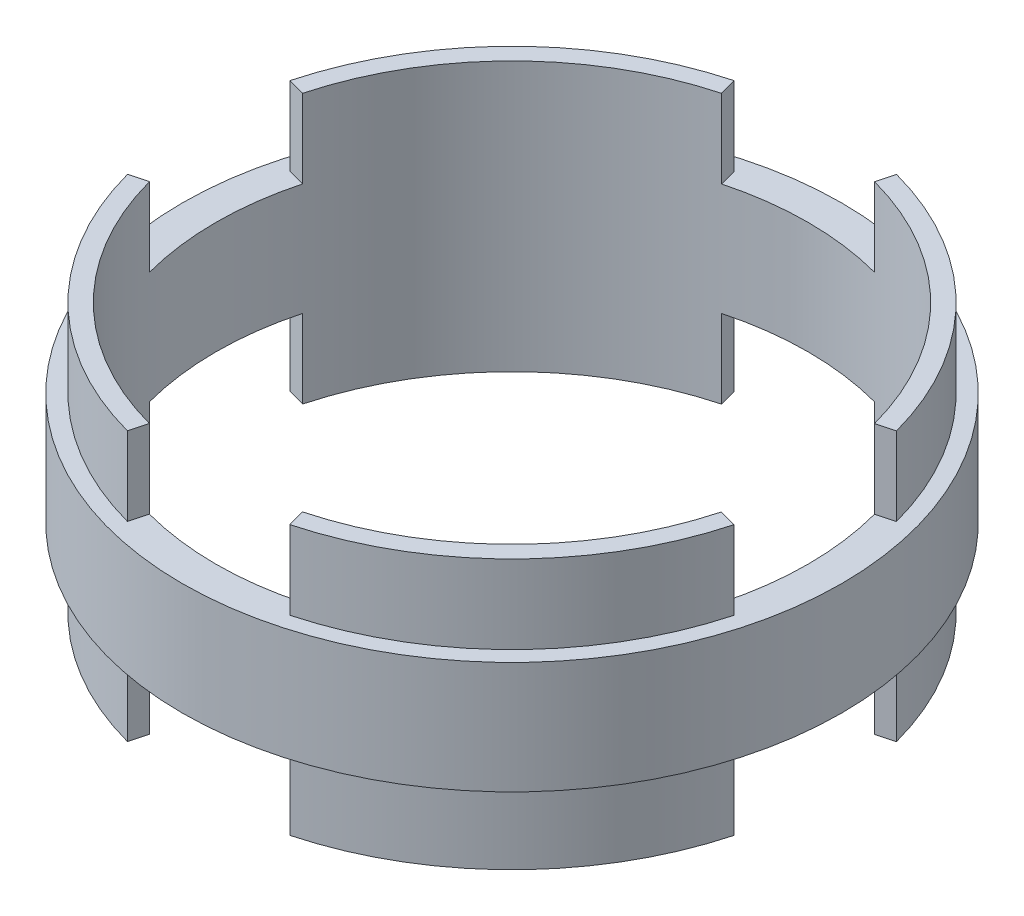
SolidWorks part; units mm, degrees
ref_plane "Front Plane" through (0, 0, 0) normal (0, 0, 1) x (1, 0, 0)
ref_plane "Top Plane" through (0, 0, 0) normal (0, 1, 0) x (1, 0, 0)
ref_plane "Right Plane" through (0, 0, 0) normal (1, 0, 0) x (0, 0, -1)
sketch "Sketch1" plane through (0, 0, 0) normal (0, 1, 0) x (1, 0, 0)
  circle A0 centre (0, 0) radius 93.345
  circle A1 centre (0, 0) radius 83.82
  dimension "D1" = 186.69
  dimension "D2" = 167.64
extrude "Boss-Extrude1" add sketch "Sketch1" along normal mid plane 31.75
sketch "Sketch2" plane through (0, 0, 0) normal (0, 1, 0) x (1, 0, 0)
  circle A0 centre (0, 0) radius 88.9
  circle A1 centre (0, 0) radius 83.82
  dimension "D1" = 177.8
  dimension "D2" = 167.64
extrude "Boss-Extrude2" add sketch "Sketch2" along normal mid plane 76.2
sketch "Sketch3" plane through (0, 0, 0) normal (0, 1, 0) x (1, 0, 0)
  line L0 (0, -116.3805) -> (0, 112.0878) construction
  line L1 (-120.9117, 0) -> (128.5432, 0) construction
  line L2 (0, 0) -> (-22.965, 85.8826)
  line L3 (0, 0) -> (23.009, 85.8708)
  circle A5 centre (0, 0) radius 88.9 construction
  arc A7 (-22.965, 85.8826) -> (23.009, 85.8708) centre (0, 0) cw
  point P7 (0, 0)
  dimension "D1" = 45.974
  dimension "D2" = 15
extrude "Cut-Extrude1" cut sketch "Sketch3" against normal mid plane 76.2
pattern_circular "CirPattern1" count 4 over 360 about axis through (0, 38.1, 0) along (0, -1, 0) of "Cut-Extrude1" reverse direction yes
sketch "Sketch4" plane through (0, 0, 0) normal (0, 1, 0) x (1, 0, 0)
  circle A0 centre (0, 0) radius 88.9
  circle A1 centre (0, 0) radius 83.82
extrude "Boss-Extrude3" add sketch "Sketch4" along normal mid plane 31.75
